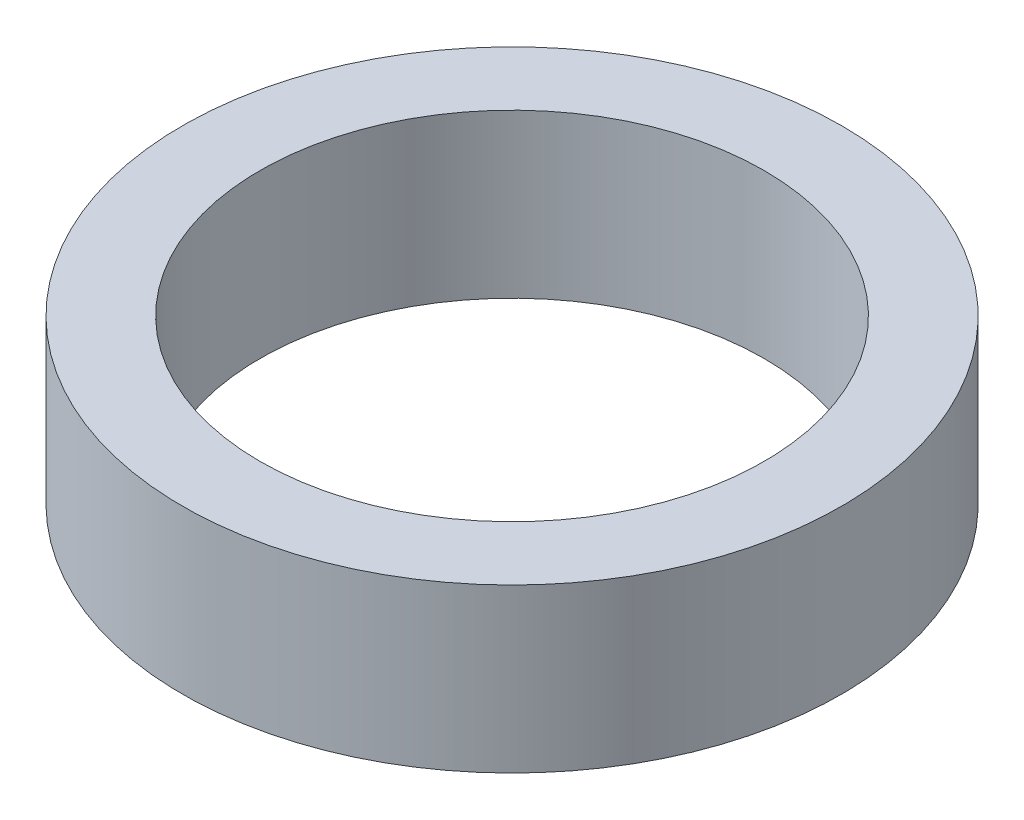
SolidWorks part; units mm, degrees
ref_plane "Front Plane" through (0, 0, 0) normal (0, 0, 1) x (1, 0, 0)
ref_plane "Top Plane" through (0, 0, 0) normal (0, 1, 0) x (1, 0, 0)
ref_plane "Right Plane" through (0, 0, 0) normal (1, 0, 0) x (0, 0, -1)
sketch "Sketch1" plane through (0, 0, 0) normal (0, 1, 0) x (1, 0, 0)
  circle A0 centre (0, 0) radius 42.5
  dimension "FLANGE_OD" = 85
extrude "Boss-Extrude1" add sketch "Sketch1" along normal blind 21
sketch "Sketch2" plane through (0, 0, 0) normal (0, 1, 0) x (1, 0, 0)
  circle A0 centre (0, 0) radius 32.5
  dimension "BORE_D" = 65
extrude "Cut-Extrude1" cut sketch "Sketch2" along normal through all
sketch "Sketch3" plane through (0, 21, 0) normal (0, 1, 0) x (1, 0, 0)
  circle A0 centre (0, 0) radius 18.868 construction
  circle A1 centre (-18.868, 0) radius 1.5809
  dimension "BOLT_D" = 3.1618
  dimension "BOLT_PCD" = 37.7361
extrude "Cut-Extrude2" cut sketch "Sketch3" against normal blind 19.463 rebuild error yes
pattern_circular "CirPattern1" count 3 over 360 rebuild error yes
